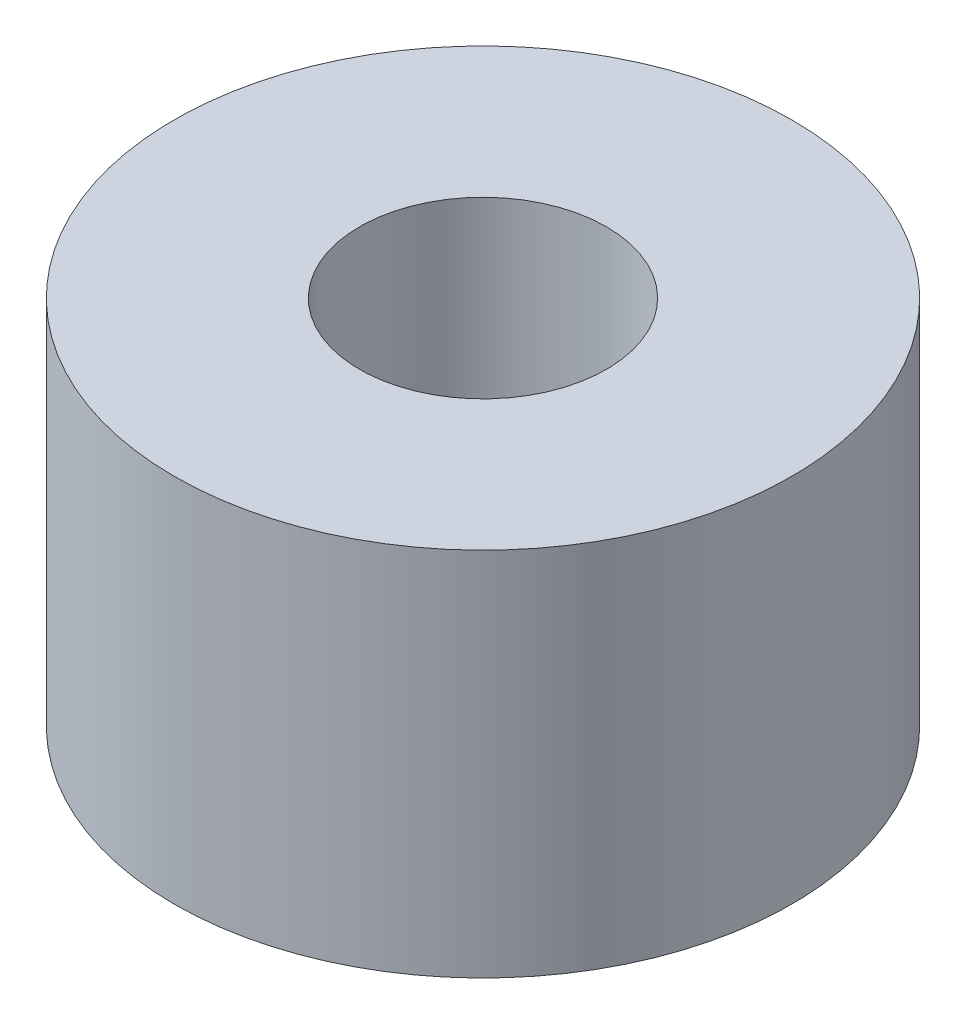
SolidWorks part; units mm, degrees
material "ABS"
ref_plane "Front Plane" through (0, 0, 0) normal (0, 0, 1) x (1, 0, 0)
ref_plane "Top Plane" through (0, 0, 0) normal (0, 1, 0) x (1, 0, 0)
ref_plane "Right Plane" through (0, 0, 0) normal (1, 0, 0) x (0, 0, -1)
sketch "Sketch1" plane through (0, 0, 0) normal (0, 0, 1) x (1, 0, 0)
  line L0 (0, 0) -> (0, 9) construction
  line L1 (0, 9) -> (3, 9) construction
  line L2 (3, 9) -> (3, 0)
  line L5 (3, 0) -> (0, 0) construction
  line L6 (3, 0) -> (7.5, 0)
  line L7 (7.5, 0) -> (7.5, 9)
  line L8 (7.5, 9) -> (3, 9)
  point P6 (3.8182, 0)
  point P8 (0, 0)
  dimension "D2" = 6
  dimension "D4" = 9
  dimension "D5" = 15
revolve "Revolve1" add sketch "Sketch1" angle 360 about L0
